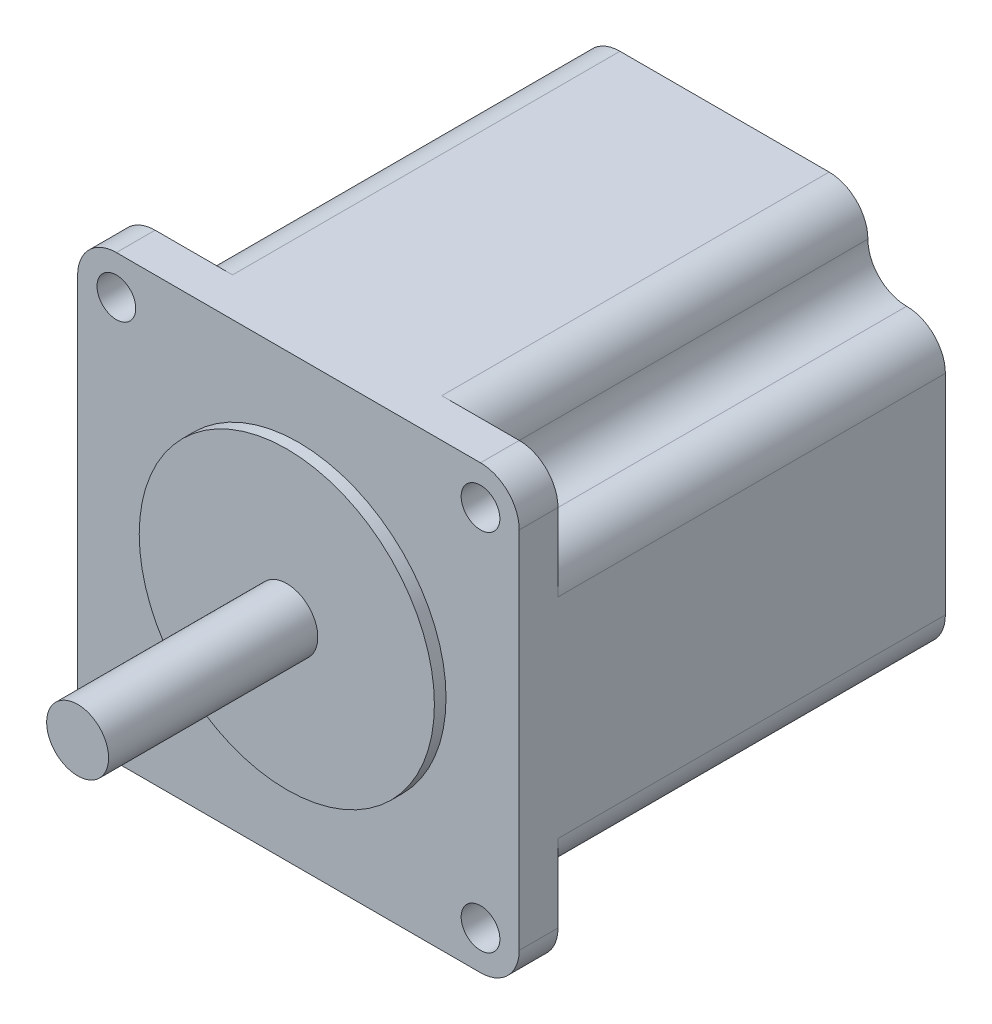
SolidWorks part; units mm, degrees
ref_plane "Front Plane" through (0, 0, 0) normal (0, 0, 1) x (1, 0, 0)
ref_plane "Top Plane" through (0, 0, 0) normal (0, 1, 0) x (1, 0, 0)
ref_plane "Right Plane" through (0, 0, 0) normal (1, 0, 0) x (0, 0, -1)
sketch "Sketch1" plane through (0, 0, 0) normal (0, 0, 1) x (1, 0, 0)
  line L1 (-33.3612, 31.2642) -> (23.6388, 31.2642)
  line L2 (-33.3612, 31.2642) -> (-33.3612, -25.7358)
  line L3 (-33.3612, -25.7358) -> (23.6388, -25.7358)
  line L4 (23.6388, 31.2642) -> (23.6388, -25.7358)
  dimension "D1" = 57
  dimension "D2" = 57
extrude "Boss-Extrude1" add sketch "Sketch1" along normal blind 55
sketch "Sketch2" plane through (0, 0, 0) normal (0, 0, -1) x (-1, 0, 0)
  line L1 (-23.6388, 31.2642) -> (-13.6388, 31.2642)
  line L2 (-23.6388, 31.2642) -> (-23.6388, 21.2642)
  line L3 (-23.6388, 21.2642) -> (-13.6388, 21.2642)
  line L4 (-13.6388, 31.2642) -> (-13.6388, 21.2642)
  dimension "D1" = 10
  dimension "D2" = 10
extrude "Cut-Extrude1" cut sketch "Sketch2" against normal blind 50
pattern_linear "LPattern1" count 2 spacing 47 along (-1, 0, 0) count 2 spacing 47 along (0, -1, 0) of "Cut-Extrude1"
sketch "Sketch3" plane through (0, 0, 55) normal (0, 0, 1) x (1, 0, 0)
  line L0 (23.6388, 31.2642) -> (-33.3612, 31.2642) construction
  line L1 (-33.3612, 31.2642) -> (-33.3612, -25.7358) construction
  circle A0 centre (-28.3612, 26.2642) radius 2.5
  dimension "D3" = 5
  dimension "D1" = 5
  dimension "D2" = 5
extrude "Cut-Extrude2" cut sketch "Sketch3" against normal blind 50
pattern_linear "LPattern2" count 2 spacing 47 along (1, 0, 0) count 2 spacing 47 along (0, -1, 0) of "Cut-Extrude2"
fillet "Fillet1" radius 5 16 edges at (-33.3612, 21.2642, 25) (-23.3612, 21.2642, 25) (-23.3612, 31.2642, 25) (13.6388, 31.2642, 25) (13.6388, 21.2642, 25) (23.6388, 21.2642, 25) (23.6388, -25.7358, 52.5) (23.6388, -15.7358, 25) (13.6388, -15.7358, 25) (13.6388, -25.7358, 25) (-23.3612, -25.7358, 25) (-23.3612, -15.7358, 25) (-33.3612, -15.7358, 25) (-33.3612, -25.7358, 52.5) (-33.3612, 31.2642, 52.5) (23.6388, 31.2642, 52.5)
sketch "Sketch5" plane through (0, 0, 55) normal (0, 0, 1) x (1, 0, 0)
  line L0 (18.6388, 31.2642) -> (-28.3612, 31.2642) construction
  line L1 (-33.3612, 26.2642) -> (-33.3612, -20.7358) construction
  circle A0 centre (-4.8612, 2.7642) radius 19.05
  dimension "D1" = 28.5
  dimension "D2" = 28.5
extrude "Boss-Extrude3" add sketch "Sketch5" along normal blind 1.5
sketch "Sketch4" plane through (0, 0, 55) normal (0, 0, 1) x (1, 0, 0)
  line L0 (18.6388, 31.2642) -> (-28.3612, 31.2642) construction
  line L1 (23.6388, -20.7358) -> (23.6388, 26.2642) construction
  circle A0 centre (-4.8612, 2.7642) radius 4
  dimension "D3" = 8
  dimension "D1" = 28.5
  dimension "D2" = 28.5
extrude "Boss-Extrude2" add sketch "Sketch4" along normal blind 28.5
